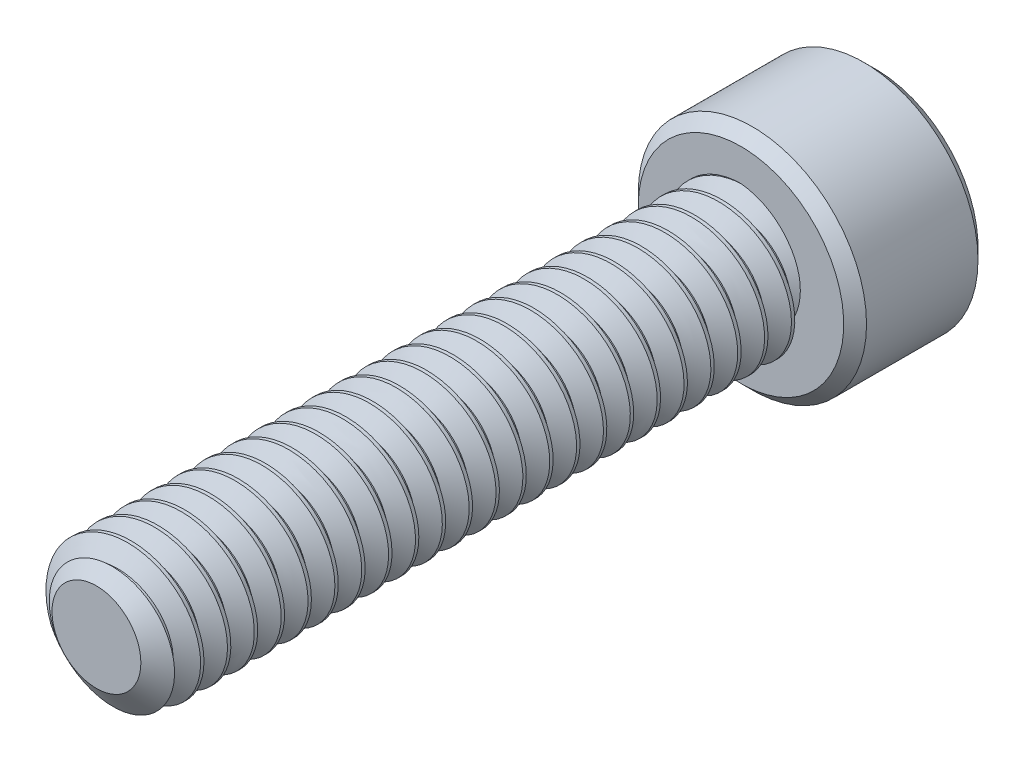
SolidWorks part; units mm, degrees
note: '?' marks a value the reader was unsure of.
other "DetailItem1"
ref_plane "Front Plane" through (0, 0, 0) normal (0, 0, 1) x (1, 0, 0)
ref_plane "Top Plane" through (0, 0, 0) normal (0, 1, 0) x (1, 0, 0)
ref_plane "Right Plane" through (0, 0, 0) normal (1, 0, 0) x (0, 0, -1)
sketch "Sketch1" plane through (0, 0, 0) normal (0, 0, 1) x (1, 0, 0)
  circle A0 centre (0, 0) radius 2.0828
  dimension "OD" = 4.1656
extrude "Extrude1" add sketch "Sketch1" against normal blind 19.05
sketch "Sketch2" plane through (0, 0, 0) normal (0, 0, 1) x (1, 0, 0)
  circle A0 centre (0, 0) radius 2.0828 construction
  circle A1 centre (0, 0) radius 2.0828
curve "Helix/Spiral1" pitch 0.7937 height 19.8438 turns 25 parameters "pitch"=0.7937
sketch "Sketch3" plane through (0, 0, 0) normal (1, 0, 0) x (0, 0, -1)
  line L0 (-0.6945, 2.0828) -> (-0.3969, 1.5672)
  line L1 (-0.3969, 1.5672) -> (-0.2977, 1.5672)
  line L2 (-0.2977, 1.5672) -> (0, 2.0828)
  line L3 (-0.6945, 2.0828) -> (0, 2.0828)
  line L4 (-0.3473, 2.0828) -> (-0.3473, 1.5672) construction
  line L5 (-0.5457, 1.825) -> (-0.1488, 1.825) construction
  line L6 (0, 2.0828) -> (0, -2.0828) construction
  dimension "D1" = 0.0992
  dimension "D2" = 0.3969
  dimension "D3" = 60
sweep "Cut-Sweep1" cut profiles "Sketch3" path "Helix/Spiral1"
sketch "Sketch4" plane through (0, 0, 0) normal (1, 0, 0) x (0, 0, -1)
  line L0 (0.5388, 2.0828) -> (0, 1.3132)
  line L1 (0, 1.3132) -> (0, 2.0828)
  line L2 (0.5388, 2.0828) -> (0, 2.0828)
  line L3 (-0.6945, 2.0828) -> (0, 2.0828) construction
  line L4 (0, 0) -> (7.0209, 0) construction
  dimension "D1" = 55
  dimension "D2" = 0.254
revolve "Cut-Revolve1" cut sketch "Sketch4" angle 360 about L4
sketch "Sketch6" plane through (0, 0, -19.05) normal (0, 0, -1) x (-1, 0, 0)
  circle A0 centre (0, 0) radius 3.3734
  dimension "head dia" = 6.7469
extrude "Extrude2" add sketch "Sketch6" along normal blind 3.9688
sketch "Sketch7" plane through (0, 0, -23.0188) normal (0, 0, -1) x (-1, 0, 0)
  line L1 (0, 2.0622) -> (-1.7859, 1.0311)
  line L2 (-1.7859, 1.0311) -> (-1.7859, -1.0311)
  line L3 (-1.7859, -1.0311) -> (0, -2.0622)
  line L4 (0, -2.0622) -> (1.7859, -1.0311)
  line L5 (1.7859, -1.0311) -> (1.7859, 1.0311)
  line L6 (1.7859, 1.0311) -> (0, 2.0622)
  circle A0 centre (0, 0) radius 1.7859 construction
  dimension "hex dia" = 3.5719
extrude "Cut-Extrude1" cut sketch "Sketch7" against normal blind 2.6789
sketch "Sketch8" plane through (0, 0, -23.0188) normal (0, 0, -1) x (-1, 0, 0)
  circle A0 centre (0, 0) radius 2.0622
extrude "Cut-Extrude2" cut sketch "Sketch8" against normal through all draft 45
chamfer "Chamfer1" distance 0.3373 angle 45 2 edges at (-3.3734, 0, -23.0188) (-3.3734, 0, -19.05)
sketch "Sketch10" plane through (0, 0, -19.05) normal (0, 0, 1) x (1, 0, 0)
  circle A1 centre (0, 0) radius 2.0828
  circle A2 centre (0, 0) radius 2.0828
  dimension "D1" = 0
ref_plane "Plane1" through (0, 0, -22.225) normal (0, 0, 1) x (1, 0, 0)
extrude "partial thread" [suppressed] add sketch "Sketch10" along normal up to surface (15.875 mm away) separate body
chamfer "Chamfer2" [suppressed] distance 0.0833 angle 45
combine bodies "Combine1" [suppressed] operation type? add bodies to combine 107 108
sketch "Sketch9" plane through (0, 0, 0) normal (1, 0, 0) x (0, 0, -1)
  line L0 (0, 2.0828) -> (0, -2.0828) construction
  line L1 (1.9844, 2.0828) -> (1.9844, -2.0828) construction
  dimension "D1" = 1.9844
equation "\"D3@Helix/Spiral1\" = \"screw length@Extrude1\"+\"pitch@Helix/Spiral1\""
equation "\"D1@Sketch3\" = \"pitch@Helix/Spiral1\"*.125"
equation "\"D2@Sketch3\" = \"pitch@Helix/Spiral1\"*.5"
equation "\"D1@Cut-Extrude1\" = \"hex dia@Sketch7\"*.75"
equation "\"D1@Chamfer1\" = \"head dia@Sketch6\"*.05"
equation "\"D1@Sketch9\" = \"pitch@Helix/Spiral1\"*2.5"
equation "\"D1@Chamfer2\"=\"OD@Sketch1\"*.02"
